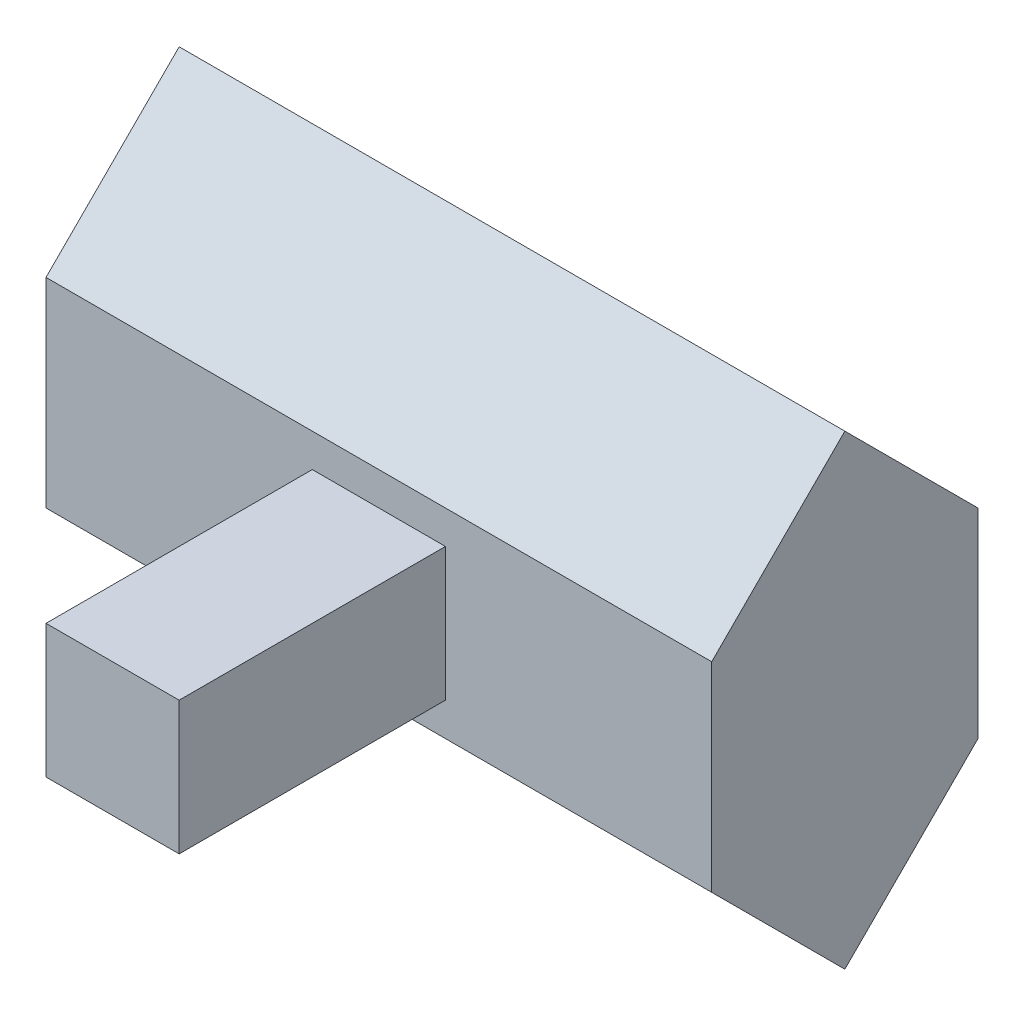
SolidWorks part; units mm, degrees
ref_plane "Front Plane" through (0, 0, 0) normal (0, 0, 1) x (1, 0, 0)
ref_plane "Top Plane" through (0, 0, 0) normal (0, 1, 0) x (1, 0, 0)
ref_plane "Right Plane" through (0, 0, 0) normal (1, 0, 0) x (0, 0, -1)
sketch "Sketch1" plane through (0, 0, 0) normal (0, 0, 1) x (1, 0, 0)
  line L1 (0, 0) -> (500, 0)
  line L2 (0, 0) -> (0, 350)
  line L3 (0, 350) -> (500, 350)
  line L4 (500, 0) -> (500, 350)
  dimension "D1" = 350
  dimension "D2" = 500
extrude "Boss-Extrude1" add sketch "Sketch1" along normal blind 200
chamfer "Chamfer3" distance 100 angle 45 4 edges at (250, 350, 0) (250, 350, 200) (250, 0, 0) (250, 0, 200)
shell "Shell2" thickness 5 removed face at (250, 175, 0)
sketch "Sketch2" plane through (0, 0, 200) normal (0, 0, 1) x (1, 0, 0)
  line L0 (500, 250) -> (0, 250) construction
  line L1 (175, 250) -> (275, 250)
  line L2 (175, 250) -> (175, 100)
  line L3 (175, 100) -> (275, 100)
  line L4 (275, 250) -> (275, 100)
  line L5 (0, 100) -> (500, 100) construction
  dimension "D1" = 100
sketch "Sketch3" plane through (0, 0, 200) normal (0, 0, 1) x (1, 0, 0)
  line L0 (175, 250) -> (275, 250) construction
  line L1 (200, 225) -> (300, 225)
  line L2 (200, 225) -> (200, 125)
  line L3 (200, 125) -> (300, 125)
  line L4 (300, 225) -> (300, 125)
  line L5 (0, 250) -> (0, 100) construction
  dimension "D1" = 100
  dimension "D2" = 100
  dimension "D3" = 25
  dimension "D4" = 200
extrude "Boss-Extrude3" add sketch "Sketch3" along normal blind 200
sketch "Sketch4" plane through (0, 225, 225) normal (0, 0.7071, 0.7071) x (1, 0, 0)
  line L4 (0, 35.3553) -> (500, 35.3553)
  line L5 (500, 35.3553) -> (500, 176.7767)
  line L6 (500, 176.7767) -> (0, 176.7767)
  line L7 (0, 176.7767) -> (0, 35.3553)
  line L8 (0, 35.3553) -> (500, 35.3553)
  line L9 (500, 35.3553) -> (500, 176.7767)
  line L10 (500, 176.7767) -> (0, 176.7767)
  line L11 (0, 176.7767) -> (0, 35.3553)
  dimension "D1" = 0
sketch "Sketch5" plane through (0, -50, 50) normal (0, -0.7071, 0.7071) x (1, 0, 0)
  line L4 (500, 212.132) -> (0, 212.132)
  line L5 (0, 212.132) -> (0, 70.7107)
  line L6 (0, 70.7107) -> (500, 70.7107)
  line L7 (500, 70.7107) -> (500, 212.132)
  line L8 (500, 212.132) -> (0, 212.132)
  line L9 (0, 212.132) -> (0, 70.7107)
  line L10 (0, 70.7107) -> (500, 70.7107)
  line L11 (500, 70.7107) -> (500, 212.132)
  dimension "D1" = 0
sketch "Sketch6" plane through (0, 225, 225) normal (0, 0.7071, 0.7071) x (1, 0, 0)
  line L4 (0, 35.3553) -> (500, 35.3553)
  line L5 (500, 35.3553) -> (500, 176.7767)
  line L6 (500, 176.7767) -> (0, 176.7767)
  line L7 (0, 176.7767) -> (0, 35.3553)
  line L8 (0, 35.3553) -> (500, 35.3553)
  line L9 (500, 35.3553) -> (500, 176.7767)
  line L10 (500, 176.7767) -> (0, 176.7767)
  line L11 (0, 176.7767) -> (0, 35.3553)
  dimension "D2" = 500
  dimension "D3" = 141.4214
  dimension "D1" = 0
sketch "Sketch7" plane through (0, 0, 0) normal (-1, 0, 0) x (0, 0, 1)
  line L6 (200, 250) -> (100, 350)
  line L7 (100, 350) -> (0, 250)
  line L8 (0, 250) -> (0, 100)
  line L9 (0, 100) -> (100, 0)
  line L10 (100, 0) -> (200, 100)
  line L11 (200, 100) -> (200, 250)
  line L12 (200, 250) -> (100, 350)
  line L13 (100, 350) -> (0, 250)
  line L14 (0, 250) -> (0, 100)
  line L15 (0, 100) -> (100, 0)
  line L16 (100, 0) -> (200, 100)
  line L17 (200, 100) -> (200, 250)
  dimension "D2" = 100
  dimension "D3" = 150
  dimension "D1" = 0
sketch "Sketch8" plane through (0, 0, 0) normal (-1, 0, 0) x (0, 0, 1)
  line L6 (200, 250) -> (100, 350)
  line L7 (100, 350) -> (0, 250)
  line L8 (0, 250) -> (0, 100)
  line L9 (0, 100) -> (100, 0)
  line L10 (100, 0) -> (200, 100)
  line L11 (200, 100) -> (200, 250)
  line L12 (200, 250) -> (100, 350)
  line L13 (100, 350) -> (0, 250)
  line L14 (0, 250) -> (0, 100)
  line L15 (0, 100) -> (100, 0)
  line L16 (100, 0) -> (200, 100)
  line L17 (200, 100) -> (200, 250)
  dimension "D1" = 0
sketch "Sketch9" plane through (200, 0, 0) normal (-1, 0, 0) x (0, 0, 1)
  line L4 (200, 225) -> (200, 125)
  line L5 (200, 125) -> (400, 125)
  line L6 (400, 125) -> (400, 225)
  line L7 (400, 225) -> (200, 225)
  line L8 (200, 225) -> (200, 125)
  line L9 (200, 125) -> (400, 125)
  line L10 (400, 125) -> (400, 225)
  line L11 (400, 225) -> (200, 225)
  dimension "D2" = 200
  dimension "D3" = 100
  dimension "D1" = 0
